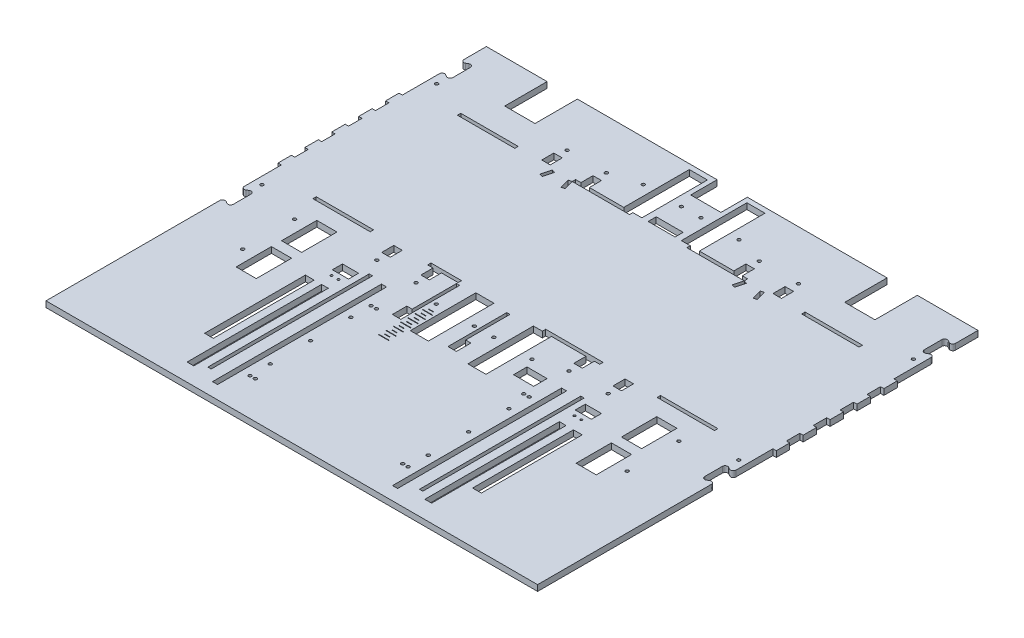
SolidWorks part; units mm, degrees
note: The reader was unsure of these and kept them because the rebuilt part matched: shared geometry of "Sketch11<3>".
material "Acrylic (Medium-high impact)"
ref_plane "Front Plane" through (0, 0, 0) normal (0, 0, 1) x (1, 0, 0)
ref_plane "Top Plane" through (0, 0, 0) normal (0, 1, 0) x (1, 0, 0)
ref_plane "Right Plane" through (0, 0, 0) normal (1, 0, 0) x (0, 0, -1)
sketch "Sketch1" plane through (0, 0, 0) normal (0, 1, 0) x (1, 0, 0)
  line L0 (0, 136.525) -> (0, -165.1) construction
  line L1 (-406.4, 136.525) -> (406.4, 136.525)
  line L2 (-406.4, 136.525) -> (-406.4, -165.1)
  line L3 (-406.4, -165.1) -> (406.4, -165.1)
  line L4 (406.4, 136.525) -> (406.4, -165.1)
  line L5 (-352.2133, 69.85) -> (-352.2133, 66.675)
  line L6 (-406.4, 69.85) -> (-352.2133, 69.85)
  line L7 (-406.4, 69.85) -> (-406.4, 66.675)
  line L8 (-406.4, 66.675) -> (-352.2133, 66.675)
  line L9 (-352.2133, 69.85) -> (-352.2133, 66.675)
  line L10 (-406.4, -66.675) -> (-352.2133, -66.675)
  line L11 (-406.4, -66.675) -> (-406.4, -69.85)
  line L12 (-406.4, -69.85) -> (-352.2133, -69.85)
  line L13 (-352.2133, -66.675) -> (-352.2133, -69.85)
  line L14 (-352.2133, 69.85) -> (-298.0267, 69.85)
  line L15 (-298.0267, 69.85) -> (-298.0267, 66.675)
  line L16 (-352.2133, 66.675) -> (-298.0267, 66.675)
  line L17 (-352.2133, -66.675) -> (-352.2133, -69.85)
  line L18 (-352.2133, -66.675) -> (-298.0267, -66.675)
  line L19 (-298.0267, -66.675) -> (-298.0267, -69.85)
  line L20 (-352.2133, -69.85) -> (-298.0267, -69.85)
  line L21 (-298.0267, 69.85) -> (-298.0267, 66.675)
  line L22 (-298.0267, 69.85) -> (-243.84, 69.85)
  line L23 (-243.84, 69.85) -> (-243.84, 66.675)
  line L24 (-298.0267, 66.675) -> (-243.84, 66.675)
  line L25 (-298.0267, -66.675) -> (-298.0267, -69.85)
  line L26 (-298.0267, -66.675) -> (-243.84, -66.675)
  line L27 (-243.84, -66.675) -> (-243.84, -69.85)
  line L28 (-298.0267, -69.85) -> (-243.84, -69.85)
  line L29 (-243.84, 69.85) -> (-243.84, 66.675)
  line L30 (-243.84, 69.85) -> (-189.6533, 69.85)
  line L31 (-189.6533, 69.85) -> (-189.6533, 66.675)
  line L32 (-243.84, 66.675) -> (-189.6533, 66.675)
  line L33 (-243.84, -66.675) -> (-243.84, -69.85)
  line L34 (-243.84, -66.675) -> (-189.6533, -66.675)
  line L35 (-189.6533, -66.675) -> (-189.6533, -69.85)
  line L36 (-243.84, -69.85) -> (-189.6533, -69.85)
  line L37 (-189.6533, 69.85) -> (-189.6533, 66.675)
  line L38 (-189.6533, 69.85) -> (-135.4667, 69.85)
  line L39 (-135.4667, 69.85) -> (-135.4667, 66.675)
  line L40 (-189.6533, 66.675) -> (-135.4667, 66.675)
  line L41 (-189.6533, -66.675) -> (-189.6533, -69.85)
  line L42 (-189.6533, -66.675) -> (-135.4667, -66.675)
  line L43 (-135.4667, -66.675) -> (-135.4667, -69.85)
  line L44 (-189.6533, -69.85) -> (-135.4667, -69.85)
  line L45 (-135.4667, 69.85) -> (-135.4667, 66.675)
  line L46 (-135.4667, 69.85) -> (-81.28, 69.85)
  line L47 (-81.28, 69.85) -> (-81.28, 66.675)
  line L48 (-135.4667, 66.675) -> (-81.28, 66.675)
  line L49 (-135.4667, -66.675) -> (-135.4667, -69.85)
  line L50 (-135.4667, -66.675) -> (-81.28, -66.675)
  line L51 (-81.28, -66.675) -> (-81.28, -69.85)
  line L52 (-135.4667, -69.85) -> (-81.28, -69.85)
  line L53 (-81.28, 69.85) -> (-81.28, 66.675)
  line L54 (-81.28, 69.85) -> (-27.0933, 69.85)
  line L55 (-27.0933, 69.85) -> (-27.0933, 66.675)
  line L56 (-81.28, 66.675) -> (-27.0933, 66.675)
  line L57 (-81.28, -66.675) -> (-81.28, -69.85)
  line L58 (-81.28, -66.675) -> (-27.0933, -66.675)
  line L59 (-27.0933, -66.675) -> (-27.0933, -69.85)
  line L60 (-81.28, -69.85) -> (-27.0933, -69.85)
  line L61 (-27.0933, 69.85) -> (-27.0933, 66.675)
  line L62 (-27.0933, 69.85) -> (27.0933, 69.85)
  line L63 (27.0933, 69.85) -> (27.0933, 66.675)
  line L64 (-27.0933, 66.675) -> (27.0933, 66.675)
  line L65 (-27.0933, -66.675) -> (-27.0933, -69.85)
  line L66 (-27.0933, -66.675) -> (27.0933, -66.675)
  line L67 (27.0933, -66.675) -> (27.0933, -69.85)
  line L68 (-27.0933, -69.85) -> (27.0933, -69.85)
  line L69 (27.0933, 69.85) -> (27.0933, 66.675)
  line L70 (27.0933, 69.85) -> (81.28, 69.85)
  line L71 (81.28, 69.85) -> (81.28, 66.675)
  line L72 (27.0933, 66.675) -> (81.28, 66.675)
  line L73 (27.0933, -66.675) -> (27.0933, -69.85)
  line L74 (27.0933, -66.675) -> (81.28, -66.675)
  line L75 (81.28, -66.675) -> (81.28, -69.85)
  line L76 (27.0933, -69.85) -> (81.28, -69.85)
  line L77 (81.28, 69.85) -> (81.28, 66.675)
  line L78 (81.28, 69.85) -> (135.4667, 69.85)
  line L79 (135.4667, 69.85) -> (135.4667, 66.675)
  line L80 (81.28, 66.675) -> (135.4667, 66.675)
  line L81 (81.28, -66.675) -> (81.28, -69.85)
  line L82 (81.28, -66.675) -> (135.4667, -66.675)
  line L83 (135.4667, -66.675) -> (135.4667, -69.85)
  line L84 (81.28, -69.85) -> (135.4667, -69.85)
  line L85 (135.4667, 69.85) -> (135.4667, 66.675)
  line L86 (135.4667, 69.85) -> (189.6533, 69.85)
  line L87 (189.6533, 69.85) -> (189.6533, 66.675)
  line L88 (135.4667, 66.675) -> (189.6533, 66.675)
  line L89 (135.4667, -66.675) -> (135.4667, -69.85)
  line L90 (135.4667, -66.675) -> (189.6533, -66.675)
  line L91 (189.6533, -66.675) -> (189.6533, -69.85)
  line L92 (135.4667, -69.85) -> (189.6533, -69.85)
  line L93 (189.6533, 69.85) -> (189.6533, 66.675)
  line L94 (189.6533, 69.85) -> (243.84, 69.85)
  line L95 (243.84, 69.85) -> (243.84, 66.675)
  line L96 (189.6533, 66.675) -> (243.84, 66.675)
  line L97 (189.6533, -66.675) -> (189.6533, -69.85)
  line L98 (189.6533, -66.675) -> (243.84, -66.675)
  line L99 (243.84, -66.675) -> (243.84, -69.85)
  line L100 (189.6533, -69.85) -> (243.84, -69.85)
  line L101 (243.84, 69.85) -> (243.84, 66.675)
  line L102 (243.84, 69.85) -> (298.0267, 69.85)
  line L103 (298.0267, 69.85) -> (298.0267, 66.675)
  line L104 (243.84, 66.675) -> (298.0267, 66.675)
  line L105 (243.84, -66.675) -> (243.84, -69.85)
  line L106 (243.84, -66.675) -> (298.0267, -66.675)
  line L107 (298.0267, -66.675) -> (298.0267, -69.85)
  line L108 (243.84, -69.85) -> (298.0267, -69.85)
  line L109 (298.0267, 69.85) -> (298.0267, 66.675)
  line L110 (298.0267, 69.85) -> (352.2133, 69.85)
  line L111 (352.2133, 69.85) -> (352.2133, 66.675)
  line L112 (298.0267, 66.675) -> (352.2133, 66.675)
  line L113 (298.0267, -66.675) -> (298.0267, -69.85)
  line L114 (298.0267, -66.675) -> (352.2133, -66.675)
  line L115 (352.2133, -66.675) -> (352.2133, -69.85)
  line L116 (298.0267, -69.85) -> (352.2133, -69.85)
  line L117 (352.2133, 69.85) -> (352.2133, 66.675)
  line L118 (352.2133, 69.85) -> (406.4, 69.85)
  line L119 (406.4, 69.85) -> (406.4, 66.675)
  line L120 (352.2133, 66.675) -> (406.4, 66.675)
  line L121 (352.2133, -66.675) -> (352.2133, -69.85)
  line L122 (352.2133, -66.675) -> (406.4, -66.675)
  line L123 (406.4, -66.675) -> (406.4, -69.85)
  line L124 (352.2133, -69.85) -> (406.4, -69.85)
  line L125 (-54.1867, 66.675) -> (-54.1867, -66.675) construction
  line L126 (-381, 57.15) -> (-381, 44.45)
  line L127 (-381, 69.85) -> (-377.825, 69.85)
  line L128 (-381, 69.85) -> (-381, 57.15)
  line L129 (-381, 57.15) -> (-377.825, 57.15)
  line L130 (-377.825, 69.85) -> (-377.825, 57.15)
  line L131 (377.825, 69.85) -> (381, 69.85)
  line L132 (377.825, 69.85) -> (377.825, 57.15)
  line L133 (377.825, 57.15) -> (381, 57.15)
  line L134 (381, 69.85) -> (381, 57.15)
  line L135 (-381, 57.15) -> (-377.825, 57.15)
  line L136 (-377.825, 57.15) -> (-377.825, 44.45)
  line L137 (-381, 44.45) -> (-377.825, 44.45)
  line L138 (377.825, 57.15) -> (377.825, 44.45)
  line L139 (377.825, 57.15) -> (381, 57.15)
  line L140 (381, 57.15) -> (381, 44.45)
  line L141 (377.825, 44.45) -> (381, 44.45)
  line L142 (-381, 44.45) -> (-381, 31.75)
  line L143 (-381, 44.45) -> (-377.825, 44.45)
  line L144 (-377.825, 44.45) -> (-377.825, 31.75)
  line L145 (-381, 31.75) -> (-377.825, 31.75)
  line L146 (377.825, 44.45) -> (377.825, 31.75)
  line L147 (377.825, 44.45) -> (381, 44.45)
  line L148 (381, 44.45) -> (381, 31.75)
  line L149 (377.825, 31.75) -> (381, 31.75)
  line L150 (-381, 31.75) -> (-381, 19.05)
  line L151 (-381, 31.75) -> (-377.825, 31.75)
  line L152 (-377.825, 31.75) -> (-377.825, 19.05)
  line L153 (-381, 19.05) -> (-377.825, 19.05)
  line L154 (377.825, 31.75) -> (377.825, 19.05)
  line L155 (377.825, 31.75) -> (381, 31.75)
  line L156 (381, 31.75) -> (381, 19.05)
  line L157 (377.825, 19.05) -> (381, 19.05)
  line L158 (-381, 19.05) -> (-381, 6.35)
  line L159 (-381, 19.05) -> (-377.825, 19.05)
  line L160 (-377.825, 19.05) -> (-377.825, 6.35)
  line L161 (-381, 6.35) -> (-377.825, 6.35)
  line L162 (377.825, 19.05) -> (377.825, 6.35)
  line L163 (377.825, 19.05) -> (381, 19.05)
  line L164 (381, 19.05) -> (381, 6.35)
  line L165 (377.825, 6.35) -> (381, 6.35)
  line L166 (-381, 6.35) -> (-381, -6.35)
  line L167 (-381, 6.35) -> (-377.825, 6.35)
  line L168 (-377.825, 6.35) -> (-377.825, -6.35)
  line L169 (-381, -6.35) -> (-377.825, -6.35)
  line L170 (377.825, 6.35) -> (377.825, -6.35)
  line L171 (377.825, 6.35) -> (381, 6.35)
  line L172 (381, 6.35) -> (381, -6.35)
  line L173 (377.825, -6.35) -> (381, -6.35)
  line L174 (-381, -6.35) -> (-381, -19.05)
  line L175 (-381, -6.35) -> (-377.825, -6.35)
  line L176 (-377.825, -6.35) -> (-377.825, -19.05)
  line L177 (-381, -19.05) -> (-377.825, -19.05)
  line L178 (377.825, -6.35) -> (377.825, -19.05)
  line L179 (377.825, -6.35) -> (381, -6.35)
  line L180 (381, -6.35) -> (381, -19.05)
  line L181 (377.825, -19.05) -> (381, -19.05)
  line L182 (-381, -19.05) -> (-381, -31.75)
  line L183 (-381, -19.05) -> (-377.825, -19.05)
  line L184 (-377.825, -19.05) -> (-377.825, -31.75)
  line L185 (-381, -31.75) -> (-377.825, -31.75)
  line L186 (377.825, -19.05) -> (377.825, -31.75)
  line L187 (377.825, -19.05) -> (381, -19.05)
  line L188 (381, -19.05) -> (381, -31.75)
  line L189 (377.825, -31.75) -> (381, -31.75)
  line L190 (-381, -31.75) -> (-381, -44.45)
  line L191 (-381, -31.75) -> (-377.825, -31.75)
  line L192 (-377.825, -31.75) -> (-377.825, -44.45)
  line L193 (-381, -44.45) -> (-377.825, -44.45)
  line L194 (377.825, -31.75) -> (377.825, -44.45)
  line L195 (377.825, -31.75) -> (381, -31.75)
  line L196 (381, -31.75) -> (381, -44.45)
  line L197 (377.825, -44.45) -> (381, -44.45)
  line L198 (-381, -44.45) -> (-381, -57.15)
  line L199 (-381, -44.45) -> (-377.825, -44.45)
  line L200 (-377.825, -44.45) -> (-377.825, -57.15)
  line L201 (-381, -57.15) -> (-377.825, -57.15)
  line L202 (377.825, -44.45) -> (377.825, -57.15)
  line L203 (377.825, -44.45) -> (381, -44.45)
  line L204 (381, -44.45) -> (381, -57.15)
  line L205 (377.825, -57.15) -> (381, -57.15)
  line L206 (-381, -57.15) -> (-381, -69.85)
  line L207 (-381, -57.15) -> (-377.825, -57.15)
  line L208 (-377.825, -57.15) -> (-377.825, -69.85)
  line L209 (-381, -69.85) -> (-377.825, -69.85)
  line L210 (377.825, -57.15) -> (377.825, -69.85)
  line L211 (377.825, -57.15) -> (381, -57.15)
  line L212 (381, -57.15) -> (381, -69.85)
  line L213 (377.825, -69.85) -> (381, -69.85)
  line L214 (-377.825, 0) -> (377.825, 0) construction
  point P23 (-54.1867, 0)
  point P133 (0, 0)
  dimension "D1" = 301.625
  dimension "D2" = 812.8
  dimension "D3" = 3.175
  dimension "D5" = 54.1867
  dimension "D6" = 66.675
  dimension "D7" = 133.35
  dimension "D9" = 12.7
  dimension "D10" = 755.65
  dimension "D4" = 15
  dimension "D8" = 11
extrude "Main Extrude" add sketch "Sketch1" along normal blind 5.588 contours L124 L116 L108 L100 L92 L84 L76 L68 L60 L52 L44 L36 L28 L20 L12 L2 L3 L4 | L210 L202 L194 L186 L178 L170 L162 L154 L146 L138 L132 L120 L112 L104 L96 L88 L80 L72 L64 L56 L48 L40 L32 L24 L16 L8 L130 L136 L144 L152 L160 L168 L176 L184 L192 L200 L208 L10 L18 L26 L34 L42 L50 L58 L66 L74 L82 L90 L98 L106 L114 | L110 L118 L4 L1 L2 L6 L14 L22 L30 L38 L46 L54 L62 L70 L78 L86 L94 L102 | L206 L198 L190 L182 L174 L166 L158 L150 L142 L126 L128 L8 L2 L10 | L204 L212 L122 L4 L120 L134 L140 L148 L156 L164 L172 L180 L188 L196 | L126 L137 L136 L129 | L150 L153 L152 L145 | L166 L169 L168 L161 | L182 L185 L184 L177 | L198 L201 L200 L193 | L13 L20 L19 L18 | L5 L16 L15 L14 | L23 L32 L31 L30 | L27 L36 L35 L34 | L43 L52 L51 L50 | L39 L48 L47 L46 | L55 L64 L63 L62 | L59 L68 L67 L66 | L71 L80 L79 L78 | L75 L84 L83 L82 | L87 L96 L95 L94 | L103 L112 L111 L110 | L91 L100 L99 L98 | L107 L116 L115 L114 | L138 L141 L140 L133 | L154 L157 L156 L149 | L170 L173 L172 L165 | L186 L189 L188 L181 | L202 L205 L204 L197
sketch "Sketch2" plane through (0, 5.588, 0) normal (0, 1, 0) x (1, 0, 0)
  line L0 (-90.678, 66.675) -> (-90.678, -110.1521) construction
  line L1 (-81.28, 66.675) -> (-27.0933, 66.675) construction
  line L3 (90.678, 66.675) -> (90.678, -110.1521) construction
  line L4 (27.0933, 66.675) -> (81.28, 66.675) construction
  line L5 (-90.678, -21.7386) -> (90.678, -21.7386) construction
  line L6 (-81.28, -66.675) -> (-27.0933, -66.675) construction
  line L7 (-52.578, -66.675) -> (-1.778, -66.675) construction
  line L8 (-52.578, -66.675) -> (-52.578, -36.2354) construction
  line L9 (-52.578, -36.2354) -> (-1.778, -36.2354) construction
  line L10 (-1.778, -66.675) -> (-1.778, -36.2354) construction
  line L11 (-26.543, 63.5) -> (26.543, 63.5) construction
  line L12 (13.843, -60.325) -> (40.513, -60.325) construction
  line L13 (13.843, -60.325) -> (13.843, -66.675) construction
  line L14 (13.843, -66.675) -> (40.513, -66.675) construction
  line L15 (40.513, -60.325) -> (40.513, -66.675) construction
  line L16 (-53.213, 66.675) -> (-26.543, 66.675) construction
  line L17 (-53.213, 66.675) -> (-53.213, 60.325) construction
  line L18 (-53.213, 60.325) -> (-26.543, 60.325) construction
  line L19 (-26.543, 66.675) -> (-26.543, 60.325) construction
  line L20 (26.543, 66.675) -> (53.213, 66.675) construction
  line L21 (26.543, 66.675) -> (26.543, 60.325) construction
  line L22 (26.543, 60.325) -> (53.213, 60.325) construction
  line L23 (53.213, 66.675) -> (53.213, 60.325) construction
  line L24 (27.0933, -66.675) -> (81.28, -66.675) construction
  point P4 (0, -21.7386)
  point P23 (-27.178, -36.2354)
  point P24 (27.178, -60.325)
  point P34 (0, 63.5)
  point P35 (-39.878, 66.675)
  dimension "D1" = 181.356
  dimension "D2" = 50.8
  dimension "D3" = 63.5
  dimension "D4" = 26.67
  dimension "D5" = 63.5
  dimension "D6" = 50.8
  dimension "D7" = 6.35
sketch "Sketch3" plane through (0, 5.588, 0) normal (0, 1, 0) x (1, 0, 0)
  line L1 (-52.578, -66.675) -> (-27.0933, -66.675)
  line L2 (-52.578, -66.675) -> (-52.578, -69.85)
  line L3 (-52.578, -69.85) -> (-27.0933, -69.85)
  line L4 (-27.0933, -66.675) -> (-27.0933, -69.85)
extrude "Under Trough Fill" add sketch "Sketch3" against normal up to surface (5.588 mm away) up to face at (0, 0, 1.5875)
sketch "Sketch4" plane through (0, 5.588, 0) normal (0, 1, 0) x (1, 0, 0)
  line L0 (-27.178, 66.675) -> (27.178, 66.675) construction
  line L2 (-406.4, 136.525) -> (406.4, 136.525) construction
  line L3 (27.0933, -69.85) -> (81.28, -69.85) construction
  line L4 (27.0933, 66.675) -> (81.28, 66.675) construction
  line L5 (27.178, -131.7625) -> (27.178, -66.675) construction
  line L6 (13.843, -66.675) -> (40.513, -66.675) construction
  line L7 (27.178, 131.7625) -> (27.178, 66.675) construction
  line L8 (-406.4, 66.675) -> (-406.4, -66.675) construction
  line L9 (-27.178, 131.7625) -> (-27.178, 66.675) construction
  line L11 (-406.4, -66.675) -> (-381, -66.675) construction
  line L12 (-400.05, -66.675) -> (-387.35, -66.675)
  line L13 (-400.05, -66.675) -> (-400.05, -63.5)
  line L14 (-400.05, -63.5) -> (-387.35, -63.5)
  line L15 (-387.35, -66.675) -> (-387.35, -63.5)
  line L16 (-406.4, 66.675) -> (-381, 66.675) construction
  line L17 (-400.05, 66.675) -> (-387.35, 66.675)
  line L18 (-400.05, 66.675) -> (-400.05, 63.5)
  line L19 (-400.05, 63.5) -> (-387.35, 63.5)
  line L20 (-387.35, 66.675) -> (-387.35, 63.5)
  line L21 (381, 66.675) -> (406.4, 66.675) construction
  line L22 (387.35, 66.675) -> (400.05, 66.675)
  line L23 (387.35, 66.675) -> (387.35, 63.5)
  line L24 (387.35, 63.5) -> (400.05, 63.5)
  line L25 (400.05, 66.675) -> (400.05, 63.5)
  line L26 (381, -66.675) -> (406.4, -66.675) construction
  line L27 (387.35, -66.675) -> (400.05, -66.675)
  line L28 (387.35, -66.675) -> (387.35, -63.5)
  line L29 (387.35, -63.5) -> (400.05, -63.5)
  line L30 (400.05, -66.675) -> (400.05, -63.5)
  line L35 (406.4, 66.675) -> (406.4, -66.675) construction
  line L36 (-81.28, 69.85) -> (-27.0933, 69.85) construction
  line L39 (27.0933, 69.85) -> (81.28, 69.85) construction
  line L40 (18.628, -69.85) -> (35.728, -69.85)
  line L41 (18.628, -69.85) -> (18.628, -131.7625)
  line L42 (18.628, -131.7625) -> (35.728, -131.7625)
  line L43 (35.728, -69.85) -> (35.728, -131.7625)
  line L44 (18.628, 131.7625) -> (35.728, 131.7625)
  line L45 (18.628, 131.7625) -> (18.628, 69.85)
  line L46 (18.628, 69.85) -> (35.728, 69.85)
  line L47 (35.728, 131.7625) -> (35.728, 69.85)
  line L48 (9.178, -97.7625) -> (45.178, -97.7625) construction
  line L49 (-35.728, 131.7625) -> (-18.628, 131.7625)
  line L50 (-35.728, 131.7625) -> (-35.728, 69.85)
  line L51 (-35.728, 69.85) -> (-18.628, 69.85)
  line L52 (-18.628, 131.7625) -> (-18.628, 69.85)
  line L53 (-45.178, 97.7625) -> (-9.178, 97.7625) construction
  line L54 (9.178, 97.7625) -> (45.178, 97.7625) construction
  circle A12 centre (9.178, -97.7625) radius 1.5
  circle A13 centre (45.178, -97.7625) radius 1.5
  circle A14 centre (9.178, 97.7625) radius 1.5
  circle A15 centre (45.178, 97.7625) radius 1.5
  circle A16 centre (-9.178, 97.7625) radius 1.5
  circle A17 centre (-45.178, 97.7625) radius 1.5
  point P2 (0, 136.525)
  point P3 (0, 66.675)
  point P59 (-393.7, -63.5)
  point P62 (393.7, -66.675)
  point P73 (27.178, -69.85)
  point P87 (27.178, 131.7625)
  point P92 (-27.178, 131.7625)
  point P100 (27.178, -97.7625)
  point P106 (-27.178, 97.7625)
  point P107 (27.178, 97.7625)
  dimension "D2" = 37.256
  dimension "D15" = 3
  dimension "D4" = 12.7
  dimension "D5" = 3.175
  dimension "D6" = 12.7
  dimension "D7" = 12.7
  dimension "D12" = 17.1
  dimension "D13" = 61.9125
  dimension "D14" = 36
  dimension "D16" = 27.9125
  dimension "D17" = 27.9125
extrude "Lever Holes" cut sketch "Sketch4" against normal through all
sketch "Sketch5" plane through (0, 5.588, 0) normal (0, 1, 0) x (1, 0, 0)
  line L0 (-27.178, -131.7625) -> (-27.178, -69.85) construction
  line L1 (-49.428, -99.2124) -> (-4.928, -99.2124) construction
  line L2 (-52.428, -127) -> (-49.428, -127)
  line L3 (-52.428, -127) -> (-52.428, -71.4248)
  line L4 (-52.428, -71.4248) -> (-49.428, -71.4248)
  line L5 (-49.428, -127) -> (-49.428, -71.4248)
  line L6 (-4.928, -127) -> (-1.928, -127)
  line L7 (-4.928, -127) -> (-4.928, -71.4248)
  line L8 (-4.928, -71.4248) -> (-1.928, -71.4248)
  line L9 (-1.928, -127) -> (-1.928, -71.4248)
  line L10 (-27.178, -66.675) -> (-27.178, -99.2124) construction
  line L11 (-52.578, -66.675) -> (-1.778, -66.675) construction
  line L12 (-35.728, -69.85) -> (-18.628, -69.85)
  line L13 (-81.28, -69.85) -> (-52.578, -69.85) construction
  line L14 (-55.778, -71.9185) -> (-4.928, -71.9185) construction
  line L15 (-35.728, -69.85) -> (-35.728, -131.7625)
  line L16 (-52.578, -66.675) -> (-52.578, -69.85) construction
  line L17 (-52.428, -127) -> (-57.428, -127)
  line L18 (-52.428, -127) -> (-52.428, -113.3)
  line L19 (-52.428, -113.3) -> (-57.428, -113.3)
  line L20 (-57.428, -127) -> (-57.428, -113.3)
  line L21 (-1.928, -127) -> (3.072, -127)
  line L22 (-1.928, -127) -> (-1.928, -113.3)
  line L23 (-1.928, -113.3) -> (3.072, -113.3)
  line L24 (3.072, -127) -> (3.072, -113.3)
  line L25 (-52.578, -66.675) -> (-52.428, -66.675)
  line L26 (-52.578, -66.675) -> (-52.578, -69.85)
  line L27 (-52.578, -69.85) -> (-52.428, -69.85)
  line L28 (-52.428, -66.675) -> (-52.428, -69.85)
  line L29 (-35.728, -131.7625) -> (-18.628, -131.7625)
  line L30 (-18.628, -69.85) -> (-18.628, -131.7625)
  line L31 (-81.28, -69.85) -> (-52.578, -69.85) construction
  circle A0 centre (-9.178, -97.7625) radius 1.5
  circle A2 centre (-45.178, -97.7625) radius 1.5
  point P19 (-50.928, -127)
  point P20 (-3.428, -127)
  dimension "D6" = 3
  dimension "D1" = 3
  dimension "D3" = 47.5
  dimension "D4" = 57.15
  dimension "D7" = 5
  dimension "D8" = 13.7
  dimension "D2" = 1.5748
  dimension "D5" = 17.1
  dimension "D9" = 61.9125
  dimension "D10" = 13.7
  dimension "D11" = 9.45
  dimension "D12" = 34
extrude "Trough Slot" cut sketch "Sketch5" against normal through all
sketch "Sketch6" plane through (0, 5.588, 0) normal (0, 1, 0) x (1, 0, 0)
  line L0 (90.678, -130.35) -> (103.378, -130.35) construction
  line L1 (-114.6905, -123.85) -> (114.6905, -123.85) construction
  line L3 (-81.28, -69.85) -> (-52.428, -69.85) construction
  line L4 (111.4405, -123.85) -> (117.9405, -123.85) construction
  line L5 (95.4405, -130.35) -> (95.4405, -83.0238) construction
  line L6 (90.678, 66.675) -> (90.678, -110.1521) construction
  line L7 (0, -21.7386) -> (0, -165.1) construction
  line L8 (-90.678, -21.7386) -> (90.678, -21.7386) construction
  line L9 (-406.4, -165.1) -> (406.4, -165.1) construction
  line L20 (-117.9405, -123.85) -> (-111.4405, -123.85) construction
  line L21 (-122.3105, -109.245) -> (-107.0705, -109.245)
  line L22 (-122.3105, -109.245) -> (-122.3105, -118.77)
  line L23 (-122.3105, -118.77) -> (-107.0705, -118.77)
  line L24 (-107.0705, -109.245) -> (-107.0705, -118.77)
  line L25 (107.0705, -109.245) -> (122.3105, -109.245)
  line L26 (107.0705, -109.245) -> (107.0705, -118.77)
  line L27 (107.0705, -118.77) -> (122.3105, -118.77)
  line L28 (122.3105, -109.245) -> (122.3105, -118.77)
  line L29 (-114.6905, -118.77) -> (-114.6905, -123.85) construction
  line L30 (114.6905, -118.77) -> (114.6905, -123.85) construction
  circle A0 centre (117.9405, -123.85) radius 1.05
  circle A1 centre (111.4405, -123.85) radius 1.05
  circle A10 centre (-117.9405, -123.85) radius 1.05
  circle A11 centre (-111.4405, -123.85) radius 1.05
  point P0 (108.1405, -130.35)
  point P11 (0, -123.85)
  dimension "D5" = 2.1
  dimension "D2" = 60.5
  dimension "D3" = 6.5
  dimension "D4" = 12.7
  dimension "D6" = 6.5
  dimension "D7" = 4.7625
  dimension "D8" = 3.3
  dimension "D9" = 5.08
  dimension "D10" = 9.525
  dimension "D11" = 15.24
extrude "Close Switch Holes" cut sketch "Sketch6" against normal through all
sketch "Sketch7" plane through (0, 5.588, 0) normal (0, 1, 0) x (1, 0, 0)
  line L0 (-42.578, -149.85) -> (-42.578, -105.4) construction
  line L1 (-49.428, -127) -> (-35.728, -127) construction
  line L2 (-49.428, -127) -> (-49.428, -71.4248) construction
  line L4 (-35.728, -69.85) -> (-35.728, -131.7625) construction
  line L9 (-81.28, -69.85) -> (-52.428, -69.85) construction
  line L10 (-47.3405, -142.738) -> (-47.3405, -143.246)
  line L15 (-47.3405, -149.596) -> (-37.8155, -149.596)
  line L16 (-47.3405, -149.596) -> (-47.3405, -150.104)
  line L21 (-47.3405, -150.104) -> (-37.8155, -150.104)
  line L22 (-37.8155, -149.596) -> (-37.8155, -150.104)
  line L27 (-47.3405, -149.596) -> (-37.8155, -150.104) construction
  line L28 (-47.3405, -150.104) -> (-37.8155, -149.596) construction
  line L33 (-44.9592, -146.421) -> (-40.1967, -146.421)
  line L34 (-44.9592, -146.421) -> (-44.9592, -146.929)
  line L39 (-44.9592, -146.929) -> (-40.1967, -146.929)
  line L40 (-40.1967, -146.421) -> (-40.1967, -146.929)
  line L45 (-44.9592, -146.421) -> (-40.1967, -146.929) construction
  line L46 (-44.9592, -146.929) -> (-40.1967, -146.421) construction
  line L51 (-47.3405, -142.738) -> (-37.8155, -142.738)
  line L52 (-37.8155, -142.738) -> (-37.8155, -143.246)
  line L57 (-47.3405, -143.246) -> (-37.8155, -143.246)
  line L58 (-44.9592, -139.563) -> (-44.9592, -140.071)
  line L63 (-44.9592, -139.563) -> (-40.1967, -139.563)
  line L64 (-40.1967, -139.563) -> (-40.1967, -140.071)
  line L69 (-44.9592, -140.071) -> (-40.1967, -140.071)
  line L70 (-47.3405, -135.88) -> (-47.3405, -136.388)
  line L75 (-47.3405, -135.88) -> (-37.8155, -135.88)
  line L76 (-37.8155, -135.88) -> (-37.8155, -136.388)
  line L81 (-47.3405, -136.388) -> (-37.8155, -136.388)
  line L82 (-44.9592, -132.705) -> (-44.9592, -133.213)
  line L83 (-44.9592, -132.705) -> (-40.1967, -132.705)
  line L84 (-40.1967, -132.705) -> (-40.1967, -133.213)
  line L85 (-44.9592, -133.213) -> (-40.1967, -133.213)
  line L86 (-47.3405, -129.022) -> (-47.3405, -129.53)
  line L87 (-47.3405, -129.022) -> (-37.8155, -129.022)
  line L88 (-37.8155, -129.022) -> (-37.8155, -129.53)
  line L89 (-47.3405, -129.53) -> (-37.8155, -129.53)
  line L90 (-44.9593, -125.847) -> (-44.9593, -126.355)
  line L91 (-44.9593, -125.847) -> (-40.1968, -125.847)
  line L92 (-40.1968, -125.847) -> (-40.1968, -126.355)
  line L93 (-44.9593, -126.355) -> (-40.1968, -126.355)
  line L94 (-47.3405, -122.164) -> (-47.3405, -122.672)
  line L95 (-47.3405, -122.164) -> (-37.8155, -122.164)
  line L96 (-37.8155, -122.164) -> (-37.8155, -122.672)
  line L97 (-47.3405, -122.672) -> (-37.8155, -122.672)
  line L98 (-44.9593, -118.989) -> (-44.9593, -119.497)
  line L99 (-44.9593, -118.989) -> (-40.1968, -118.989)
  line L100 (-40.1968, -118.989) -> (-40.1968, -119.497)
  line L101 (-44.9593, -119.497) -> (-40.1968, -119.497)
  line L102 (-47.3405, -115.306) -> (-47.3405, -115.814)
  line L103 (-47.3405, -115.306) -> (-37.8155, -115.306)
  line L104 (-37.8155, -115.306) -> (-37.8155, -115.814)
  line L105 (-47.3405, -115.814) -> (-37.8155, -115.814)
  line L106 (-44.9593, -112.131) -> (-44.9593, -112.639)
  line L107 (-44.9593, -112.131) -> (-40.1968, -112.131)
  line L108 (-40.1968, -112.131) -> (-40.1968, -112.639)
  line L109 (-44.9593, -112.639) -> (-40.1968, -112.639)
  line L130 (-28.5048, -105.4) -> (-42.578, -105.4) construction
  line L136 (-47.3405, -108.448) -> (-47.3405, -108.956)
  line L137 (-47.3405, -108.448) -> (-37.8155, -108.448)
  line L138 (-37.8155, -108.448) -> (-37.8155, -108.956)
  line L139 (-47.3405, -108.956) -> (-37.8155, -108.956)
  line L140 (-44.9593, -105.273) -> (-44.9593, -105.781)
  line L141 (-44.9593, -105.273) -> (-40.1968, -105.273)
  line L142 (-40.1968, -105.273) -> (-40.1968, -105.781)
  line L143 (-44.9593, -105.781) -> (-40.1968, -105.781)
  point P2 (-42.578, -146.675)
  point P16 (-44.9592, -146.675)
  point P17 (-47.3405, -149.85)
  point P65 (-42.578, -127)
  dimension "D1" = 80
  dimension "D2" = 44.45
  dimension "D3" = 0.508
  dimension "D4" = 9.525
  dimension "D5" = 3.175
  dimension "D6" = 4.7625
  dimension "D8" = 3.175
  dimension "D7" = 7
extrude "Trough Measurement" cut sketch "Sketch7" against normal through all
sketch "Sketch8" plane through (0, 5.588, 0) normal (0, 1, 0) x (1, 0, 0)
  line L0 (160.528, 96.525) -> (160.528, -85.725) construction
  line L1 (49.063, -106.3625) -> (68.113, -106.3625)
  line L2 (49.063, -106.3625) -> (49.063, -119.0625)
  line L3 (49.063, -119.0625) -> (68.113, -119.0625)
  line L4 (68.113, -106.3625) -> (68.113, -119.0625)
  line L5 (35.728, -131.7625) -> (35.728, -69.85) construction
  line L6 (135.4667, -69.85) -> (189.6533, -69.85) construction
  line L15 (-406.4, 136.525) -> (406.4, 136.525) construction
  line L16 (-18.628, 123) -> (18.628, 123) construction
  line L17 (-18.628, 69.85) -> (-18.628, 131.7625) construction
  line L18 (18.628, 131.7625) -> (18.628, 69.85) construction
  line L19 (0, 77.47) -> (0, 96.525) construction
  line L20 (18.628, -131.7625) -> (35.728, -131.7625) construction
  line L29 (151.003, -119.0625) -> (170.053, -119.0625)
  line L30 (-174.8155, 136.525) -> (-146.2405, 136.525)
  line L31 (-14.2875, 136.525) -> (14.2875, 136.525)
  line L32 (-14.2875, 136.525) -> (-14.2875, 96.525)
  line L33 (-14.2875, 96.525) -> (14.2875, 96.525)
  line L34 (14.2875, 136.525) -> (14.2875, 96.525)
  line L35 (-12.7, 69.85) -> (12.7, 69.85)
  line L36 (-12.7, 69.85) -> (-12.7, 77.47)
  line L37 (-12.7, 77.47) -> (12.7, 77.47)
  line L38 (12.7, 69.85) -> (12.7, 77.47)
  line L39 (-27.0933, 69.85) -> (-18.628, 69.85) construction
  line L40 (151.003, -85.725) -> (170.053, -85.725)
  line L41 (151.003, -85.725) -> (151.003, -161.925)
  line L42 (151.003, -161.925) -> (170.053, -161.925)
  line L43 (170.053, -85.725) -> (170.053, -161.925)
  line L44 (-170.053, -85.725) -> (-151.003, -85.725)
  line L45 (-170.053, -85.725) -> (-170.053, -161.925)
  line L46 (-170.053, -161.925) -> (-151.003, -161.925)
  line L47 (-151.003, -85.725) -> (-151.003, -161.925)
  line L48 (90.678, 66.675) -> (90.678, -110.1521) construction
  line L49 (-151.003, -123.825) -> (151.003, -123.825) construction
  line L50 (151.003, -119.0625) -> (151.003, -128.5875)
  line L51 (151.003, -128.5875) -> (170.053, -128.5875)
  line L52 (170.053, -119.0625) -> (170.053, -128.5875)
  line L53 (-170.053, -119.0625) -> (-151.003, -119.0625)
  line L54 (-170.053, -119.0625) -> (-170.053, -128.5875)
  line L55 (-170.053, -128.5875) -> (-151.003, -128.5875)
  line L56 (-151.003, -119.0625) -> (-151.003, -128.5875)
  line L57 (-174.8155, 136.525) -> (-174.8155, 96.525)
  line L58 (-174.8155, 96.525) -> (-146.2405, 96.525)
  line L59 (-146.2405, 136.525) -> (-146.2405, 96.525)
  line L60 (146.2405, 136.525) -> (174.8155, 136.525)
  line L61 (146.2405, 136.525) -> (146.2405, 96.525)
  line L62 (146.2405, 96.525) -> (174.8155, 96.525)
  line L63 (174.8155, 136.525) -> (174.8155, 96.525)
  line L64 (-160.528, 96.525) -> (-160.528, -85.725) construction
  point P6 (58.588, -106.3625)
  point P23 (0, 123)
  point P30 (170.053, -123.825)
  point P31 (170.053, -123.825)
  point P38 (0, 96.525)
  point P61 (0, -123.825)
  dimension "D1" = 19.05
  dimension "D2" = 12.7
  dimension "D3" = 22.86
  dimension "D4" = 12.7
  dimension "D5" = 9.525
  dimension "D6" = 76.2
  dimension "D8" = 40
  dimension "D9" = 28.575
  dimension "D10" = 7.62
  dimension "D11" = 25.4
  dimension "D12" = 15.875
  dimension "D13" = 60.325
  dimension "D15" = 19.05
extrude "Wire Holes" cut sketch "Sketch8" against normal through all contours L55 L45 L46 L47 | L45 L53 L47 L44 | L51 L41 L42 L43 | L43 L40 L41 L29 | L4 L1 L2 L3 | L34 L31 L32 L33 | L35 L38 L37 L36 | L59 L30 L57 L58 | L63 L60 L61 L62
sketch "Sketch9" plane through (0, 5.588, 0) normal (0, 1, 0) x (1, 0, 0)
  line L0 (-109.2096, 89.85) -> (109.2096, 89.85) construction
  line L1 (109.2096, 89.85) -> (109.2096, -89.85) construction
  line L2 (109.2096, -89.85) -> (-109.2096, -89.85) construction
  line L3 (-109.2096, -89.85) -> (-109.2096, 89.85) construction
  line L4 (-162.56, 66.675) -> (-162.56, -66.675) construction
  line L5 (-189.6533, 66.675) -> (-135.4667, 66.675) construction
  line L6 (-189.6533, -66.675) -> (-135.4667, -66.675) construction
  line L7 (-109.2096, 0) -> (-162.56, 0) construction
  line L8 (-90.678, 66.675) -> (-90.678, -110.1521) construction
  line L9 (-189.6533, -69.85) -> (-135.4667, -69.85) construction
  line L10 (-189.6533, 69.85) -> (-135.4667, 69.85) construction
  line L11 (-113.2096, 69.85) -> (-105.2096, 69.85)
  line L12 (-113.2096, 69.85) -> (-113.2096, 81.28)
  line L13 (-113.2096, 81.28) -> (-105.2096, 81.28)
  line L14 (-105.2096, 69.85) -> (-105.2096, 81.28)
  line L16 (105.2096, 81.28) -> (113.2096, 81.28)
  line L17 (105.2096, 81.28) -> (105.2096, 69.85)
  line L18 (105.2096, 69.85) -> (113.2096, 69.85)
  line L19 (113.2096, 81.28) -> (113.2096, 69.85)
  line L20 (105.2096, -69.85) -> (113.2096, -69.85)
  line L21 (105.2096, -69.85) -> (105.2096, -81.28)
  line L22 (105.2096, -81.28) -> (113.2096, -81.28)
  line L23 (113.2096, -69.85) -> (113.2096, -81.28)
  line L24 (-113.2096, -81.28) -> (-105.2096, -81.28)
  line L25 (-113.2096, -81.28) -> (-113.2096, -69.85)
  line L26 (-113.2096, -69.85) -> (-105.2096, -69.85)
  line L27 (-105.2096, -81.28) -> (-105.2096, -69.85)
  circle A0 centre (109.2096, -89.85) radius 1.5
  circle A1 centre (-109.2096, -89.85) radius 1.5
  circle A2 centre (109.2096, 89.85) radius 1.5
  circle A3 centre (-109.2096, 89.85) radius 1.5
  point P8 (0, -89.85)
  point P29 (-109.2096, 81.28)
  point P43 (109.2096, 81.28)
  point P47 (109.2096, -69.85)
  dimension "D1" = 3
  dimension "D2" = 18.5316
  dimension "D3" = 20
  dimension "D4" = 11.43
  dimension "D5" = 8
extrude "IR Slots" cut sketch "Sketch9" against normal through all
sketch "Sketch10" plane through (0, 5.588, 0) normal (0, 1, 0) x (1, 0, 0)
  line L0 (0, 0) -> (0, 69.85) construction
  line L1 (-100.061, 66.675) -> (-96.9942, 65.8532)
  line L2 (-100.061, 66.675) -> (-102.5263, 57.4746)
  line L3 (-102.5263, 57.4746) -> (-99.4594, 56.6528)
  line L4 (-96.9942, 65.8532) -> (-99.4594, 56.6528)
  line L5 (-84.3618, 65.8532) -> (-81.295, 66.675)
  line L6 (-84.3618, 65.8532) -> (-81.8966, 56.6528)
  line L7 (-81.8966, 56.6528) -> (-78.8297, 57.4746)
  line L8 (-81.295, 66.675) -> (-78.8297, 57.4746)
  line L9 (-12.7, 69.85) -> (12.7, 69.85) construction
  line L14 (81.28, 66.675) -> (100.061, 66.675) construction
  line L19 (-90.678, 66.675) -> (-90.678, -110.1521) construction
  line L20 (-98.2268, 61.253) -> (-83.1292, 61.253) construction
  line L21 (-81.28, 66.675) -> (-100.061, 66.675) construction
  line L22 (98.2268, 61.253) -> (83.1292, 61.253) construction
  line L23 (81.295, 66.675) -> (78.8297, 57.4746)
  line L24 (81.8966, 56.6528) -> (78.8297, 57.4746)
  line L25 (84.3618, 65.8532) -> (81.8966, 56.6528)
  line L26 (84.3618, 65.8532) -> (81.295, 66.675)
  line L27 (96.9942, 65.8532) -> (99.4594, 56.6528)
  line L28 (102.5263, 57.4746) -> (99.4594, 56.6528)
  line L29 (100.061, 66.675) -> (102.5263, 57.4746)
  line L30 (100.061, 66.675) -> (96.9942, 65.8532)
  line L31 (-96.9942, 65.8532) -> (-96.774, 66.675) construction
  line L32 (-84.3618, 65.8532) -> (-84.582, 66.675) construction
  line L33 (-90.678, 66.675) -> (-90.678, 61.253) construction
  line L34 (-96.774, 66.675) -> (-95.9233, 69.85) construction
  line L35 (-84.582, 66.675) -> (-85.4327, 69.85) construction
  line L36 (-81.28, 69.85) -> (-95.9233, 69.85) construction
  point P27 (-90.678, 61.253)
  dimension "D1" = 3.175
  dimension "D3" = 9.525
  dimension "D4" = 105
  dimension "D2" = 6.096
extrude "Door Flange Slots" cut sketch "Sketch10" against normal through all
sketch "Sketch12" plane through (0, 5.588, 0) normal (0, 1, 0) x (1, 0, 0)
  line L0 (-253.5873, 82.55) -> (-225.1393, 82.55) construction
  line L1 (-253.5873, -82.55) -> (-225.1393, -82.55) construction
  line L2 (-233.807, 82.55) -> (-233.807, -82.55) construction
  line L3 (-233.807, 0) -> (0, 0) construction
  line L4 (-298.0267, -69.85) -> (-243.84, -69.85) construction
  line L5 (-240.9508, -76.2) -> (-237.7758, -76.2)
  line L6 (-240.9508, -76.2) -> (-240.9507, -88.9)
  line L7 (-240.9507, -88.9) -> (-237.7758, -88.9)
  line L8 (-237.7758, -76.2) -> (-237.7758, -88.9)
  line L9 (-240.9508, 88.9) -> (-237.7758, 88.9)
  line L10 (-240.9508, 88.9) -> (-240.9508, 76.2)
  line L11 (-240.9508, 76.2) -> (-237.7758, 76.2)
  line L12 (-237.7758, 88.9) -> (-237.7758, 76.2)
  line L13 (0, -3.0734) -> (0, 3.0734) construction
  line L14 (233.807, 82.55) -> (233.807, -82.55) construction
  line L15 (253.5873, -82.55) -> (225.1393, -82.55) construction
  line L16 (253.5873, 82.55) -> (225.1393, 82.55) construction
  line L17 (237.7758, 88.9) -> (237.7758, 76.2)
  line L18 (240.9508, 76.2) -> (237.7758, 76.2)
  line L19 (240.9508, 88.9) -> (240.9508, 76.2)
  line L20 (240.9508, 88.9) -> (237.7758, 88.9)
  line L21 (237.7757, -76.2) -> (237.7757, -88.9)
  line L22 (240.9507, -88.9) -> (237.7757, -88.9)
  line L23 (240.9507, -76.2) -> (240.9507, -88.9)
  line L24 (240.9507, -76.2) -> (237.7757, -76.2)
  circle A0 centre (-253.5873, -82.55) radius 1.5
  circle A1 centre (-225.1393, -82.55) radius 1.5
  circle A2 centre (-253.5873, 82.55) radius 1.5
  circle A3 centre (-225.1393, 82.55) radius 1.5
  circle A4 centre (225.1393, 82.55) radius 1.5
  circle A5 centre (253.5873, 82.55) radius 1.5
  circle A6 centre (225.1393, -82.55) radius 1.5
  circle A7 centre (253.5873, -82.55) radius 1.5
  point P8 (-239.3633, -76.2)
  point P9 (-239.3633, -82.55)
  point P13 (-237.7758, -82.55)
  point P14 (-239.3633, 88.9)
  point P19 (-239.3633, 82.55)
  point P22 (-240.9508, 82.55)
  dimension "D1" = 3
  dimension "D2" = 233.807
  dimension "D3" = 28.448
  dimension "D4" = 3.175
  dimension "D5" = 12.7
  dimension "D6" = 7.9375
  dimension "D7" = 12.7
extrude "Floor Mount Holes" cut sketch "Sketch12" against normal through all
sketch "Sketch11" plane through (0, 5.588, 0) normal (0, 1, 0) x (1, 0, 0)
  line L0 (-232.1306, 69.85) -> (-232.1306, 57.15)
  line L1 (-228.3206, 94.2747) -> (-226.4156, 93.1749)
  line L2 (-232.1306, 57.15) -> (-235.3056, 57.15)
  line L3 (-235.3056, 57.15) -> (-235.3056, 44.45)
  line L4 (-235.3056, 44.45) -> (-232.1306, 44.45)
  line L5 (-381, 57.15) -> (-377.825, 57.15) construction
  line L6 (-377.825, 44.45) -> (-377.825, 31.75) construction
  line L7 (-298.0267, 69.85) -> (-243.84, 69.85) construction
  line L8 (-232.1306, 44.45) -> (-232.1306, 31.75)
  line L9 (-232.1306, 31.75) -> (-235.3056, 31.75)
  line L10 (-235.3056, 31.75) -> (-235.3056, 19.05)
  line L11 (-235.3056, 19.05) -> (-232.1306, 19.05)
  line L12 (-232.1306, 19.05) -> (-232.1306, 6.35)
  line L13 (-232.1306, 6.35) -> (-235.3056, 6.35)
  line L14 (-235.3056, 6.35) -> (-235.3056, -6.35)
  line L15 (-235.3056, -6.35) -> (-232.1306, -6.35)
  line L16 (-232.1306, -6.35) -> (-232.1306, -19.05)
  line L17 (-232.1306, -19.05) -> (-235.3056, -19.05)
  line L18 (-235.3056, -19.05) -> (-235.3056, -31.75)
  line L19 (-235.3056, -31.75) -> (-232.1306, -31.75)
  line L20 (-232.1306, -31.75) -> (-232.1306, -44.45)
  line L21 (-232.1306, -44.45) -> (-235.3056, -44.45)
  line L22 (-235.3056, -44.45) -> (-235.3056, -57.15)
  line L23 (-235.3056, -57.15) -> (-232.1306, -57.15)
  line L24 (-232.1306, -57.15) -> (-232.1306, -69.85)
  line L25 (-232.1306, 69.85) -> (-232.1306, 92.075)
  line L26 (-222.6056, 95.3746) -> (-222.6056, 111.9757)
  line L27 (-226.4156, 114.1754) -> (-228.3206, 113.0756)
  line L28 (-232.1306, -118.4503) -> (-406.4, -118.4503)
  line L29 (-235.3056, -69.85) -> (-235.3056, -82.55)
  line L30 (-235.3056, -82.55) -> (-232.1306, -82.55)
  line L31 (-232.1306, -69.85) -> (-235.3056, -69.85)
  line L32 (-232.1306, -69.85) -> (-232.1306, -92.075)
  line L33 (-232.1306, 115.2753) -> (-232.1306, 136.525)
  line L34 (-406.4, 136.525) -> (-174.8155, 136.525) construction
  line L35 (-228.3206, -94.2747) -> (-226.4156, -93.1749)
  line L36 (-222.6056, -95.3746) -> (-222.6056, -111.9757)
  line L37 (-226.4156, -114.1754) -> (-228.3206, -113.0756)
  line L38 (-232.1306, -115.2753) -> (-232.1306, -165.1)
  line L39 (-406.4, -165.1) -> (406.4, -165.1) construction
  line L40 (0, -3.0734) -> (0, 3.0734) construction
  line L41 (-232.1306, 110.8759) -> (-232.1306, 96.4744) construction
  line L42 (-232.1306, -96.4744) -> (-232.1306, -110.8759) construction
  line L43 (232.1306, -96.4744) -> (232.1306, -110.8759) construction
  line L44 (232.1306, 110.8759) -> (232.1306, 96.4744) construction
  line L45 (232.1306, -115.2753) -> (232.1306, -165.1)
  line L46 (226.4156, -114.1754) -> (228.3206, -113.0756)
  line L47 (222.6056, -95.3746) -> (222.6056, -111.9757)
  line L48 (228.3206, -94.2747) -> (226.4156, -93.1749)
  line L49 (232.1306, 115.2753) -> (232.1306, 136.525)
  line L50 (232.1306, -69.85) -> (232.1306, -92.075)
  line L51 (226.4156, 114.1754) -> (228.3206, 113.0756)
  line L52 (222.6056, 95.3746) -> (222.6056, 111.9757)
  line L53 (232.1306, 69.85) -> (232.1306, 92.075)
  line L54 (232.1306, -57.15) -> (232.1306, -69.85)
  line L55 (235.3056, -57.15) -> (232.1306, -57.15)
  line L56 (235.3056, -44.45) -> (235.3056, -57.15)
  line L57 (232.1306, -44.45) -> (235.3056, -44.45)
  line L58 (232.1306, -31.75) -> (232.1306, -44.45)
  line L59 (235.3056, -31.75) -> (232.1306, -31.75)
  line L60 (235.3056, -19.05) -> (235.3056, -31.75)
  line L61 (232.1306, -19.05) -> (235.3056, -19.05)
  line L62 (232.1306, -6.35) -> (232.1306, -19.05)
  line L63 (235.3056, -6.35) -> (232.1306, -6.35)
  line L64 (235.3056, 6.35) -> (235.3056, -6.35)
  line L65 (232.1306, 6.35) -> (235.3056, 6.35)
  line L66 (232.1306, 19.05) -> (232.1306, 6.35)
  line L67 (235.3056, 19.05) -> (232.1306, 19.05)
  line L68 (235.3056, 31.75) -> (235.3056, 19.05)
  line L69 (232.1306, 31.75) -> (235.3056, 31.75)
  line L70 (232.1306, 44.45) -> (232.1306, 31.75)
  line L71 (235.3056, 44.45) -> (232.1306, 44.45)
  line L72 (235.3056, 57.15) -> (235.3056, 44.45)
  line L73 (232.1306, 57.15) -> (235.3056, 57.15)
  line L74 (228.3206, 94.2747) -> (226.4156, 93.1749)
  line L75 (232.1306, 69.85) -> (232.1306, 57.15)
  line L76 (232.1306, -118.4503) -> (406.4, -118.4503)
  line L77 (-406.4, 136.525) -> (406.4, 136.525)
  line L78 (-406.4, 136.525) -> (-406.4, -165.1)
  line L79 (-406.4, -165.1) -> (406.4, -165.1)
  line L80 (406.4, 136.525) -> (406.4, -165.1)
  arc A0 (-228.3206, 113.0756) -> (-232.1306, 115.2753) centre (-229.5906, 115.2753) cw
  arc A1 (-232.1306, 92.075) -> (-228.3206, 94.2747) centre (-229.5906, 92.075) cw
  arc A2 (-226.4156, 93.1749) -> (-222.6056, 95.3746) centre (-225.1456, 95.3746) ccw
  arc A3 (-222.6056, 111.9757) -> (-226.4156, 114.1754) centre (-225.1456, 111.9757) ccw
  arc A4 (-228.3206, -113.0756) -> (-232.1306, -115.2753) centre (-229.5906, -115.2753) ccw
  arc A5 (-232.1306, -92.075) -> (-228.3206, -94.2747) centre (-229.5906, -92.075) ccw
  arc A6 (-222.6056, -111.9757) -> (-226.4156, -114.1754) centre (-225.1456, -111.9757) cw
  arc A7 (-226.4156, -93.1749) -> (-222.6056, -95.3746) centre (-225.1456, -95.3746) cw
  arc A8 (226.4156, -93.1749) -> (222.6056, -95.3746) centre (225.1456, -95.3746) ccw
  arc A9 (222.6056, -111.9757) -> (226.4156, -114.1754) centre (225.1456, -111.9757) ccw
  arc A10 (232.1306, -92.075) -> (228.3206, -94.2747) centre (229.5906, -92.075) cw
  arc A11 (228.3206, -113.0756) -> (232.1306, -115.2753) centre (229.5906, -115.2753) cw
  arc A12 (222.6056, 111.9757) -> (226.4156, 114.1754) centre (225.1456, 111.9757) cw
  arc A13 (226.4156, 93.1749) -> (222.6056, 95.3746) centre (225.1456, 95.3746) cw
  arc A14 (232.1306, 92.075) -> (228.3206, 94.2747) centre (229.5906, 92.075) ccw
  arc A15 (228.3206, 113.0756) -> (232.1306, 115.2753) centre (229.5906, 115.2753) ccw
  circle A16 centre (-225.1393, -82.55) radius 1.5 construction
  point P60 (-222.6056, 90.9751)
  point P63 (-222.6056, 116.3751)
  point P131 (222.6056, 116.3751)
  point P132 (222.6056, 90.9751)
  dimension "D5" = 2.54
  dimension "D2" = 60
  dimension "D3" = 25.4
  dimension "D4" = 9.525
  dimension "D6" = 235.3056
  dimension "D7" = 9.525
  dimension "D8" = 3.175
  dimension "D1" = 6
extrude "Extension Side Cut" [suppressed] cut sketch "Sketch11" against normal through all
extrude "Extension Center Cut" cut sketch "Sketch11<3>" against normal through all contours A7 L35 A5 L32 L24 L23 L22 L21 L20 L19 L18 L17 L16 L15 L14 L13 L12 L11 L10 L9 L8 L4 L3 L2 L0 L25 A1 L1 A2 L26 A3 L27 A0 L33 L77 L78 L79 L38 A4 L37 A6 L36 | A15 L51 A12 L52 A13 L74 A14 L53 L75 L73 L72 L71 L70 L69 L68 L67 L66 L65 L64 L63 L62 L61 L60 L59 L58 L57 L56 L55 L54 L50 A10 L48 A8 L47 A9 L46 A11 L45 L79 L80 L77 L49 | L78 L79 L38 L28 | L80 L76 L45 L79
sketch "Sketch11<3>" plane through (0, 5.588, 0) normal (0, 1, 0) x (1, 0, 0) same geometry as "Sketch11"
sketch "Sketch13" plane through (0, 5.588, 0) normal (0, 1, 0) x (1, 0, 0)
  line L1 (-232.1306, -165.1) -> (232.1306, -165.1)
  line L2 (-232.1306, -165.1) -> (-232.1306, -279.4)
  line L3 (-232.1306, -279.4) -> (232.1306, -279.4)
  line L4 (232.1306, -165.1) -> (232.1306, -279.4)
  dimension "D1" = 114.3
extrude "Center Extend" add sketch "Sketch13" against normal up to surface (5.588 mm away) up to face at (225.1393, 0, -84.05)
sketch "Sketch15" plane through (0, 5.588, 0) normal (0, 1, 0) x (1, 0, 0)
  line L0 (98.3405, -257.175) -> (98.3405, -104.775)
  line L1 (35.728, -69.85) -> (81.28, -69.85) construction
  line L2 (98.3405, -104.775) -> (101.5155, -104.775)
  line L3 (101.5155, -104.775) -> (101.5155, -257.175)
  line L4 (101.5155, -257.175) -> (98.3405, -257.175)
  line L5 (0, -3.0734) -> (0, 3.0734) construction
  line L11 (90.678, 66.675) -> (90.678, -110.1521) construction
  line L19 (-101.5155, -257.175) -> (-98.3405, -257.175)
  line L20 (-101.5155, -104.775) -> (-101.5155, -257.175)
  line L21 (-98.3405, -104.775) -> (-101.5155, -104.775)
  line L22 (-98.3405, -257.175) -> (-98.3405, -104.775)
  point P10 (99.928, -104.775)
  dimension "D2" = 3.175
  dimension "D3" = 152.4
  dimension "D4" = 34.925
  dimension "D1" = 9.25
extrude "Track Cuts" cut sketch "Sketch15" against normal through all
sketch "Sketch18" plane through (0, 5.588, 0) normal (0, 1, 0) x (1, 0, 0)
  line L0 (-85.0154, -120.396) -> (-85.0154, -107.2515) construction
  line L1 (-87.403, -107.2515) -> (-82.6278, -107.2515)
  line L2 (-87.403, -107.2515) -> (-87.403, -266.8905)
  line L3 (-87.403, -266.8905) -> (-82.6278, -266.8905)
  line L4 (-82.6278, -107.2515) -> (-82.6278, -266.8905)
  line L5 (-81.28, 66.675) -> (-27.0933, 66.675) construction
  line L6 (-85.0154, -266.8905) -> (-85.0154, -253.746) construction
  line L7 (-90.678, 66.675) -> (-90.678, -110.1521) construction
  line L8 (-69.6103, -129.921) -> (-69.6103, -244.221) construction
  line L9 (-69.6103, -187.071) -> (-82.6278, -187.071) construction
  line L10 (0, -3.0734) -> (0, 3.0734) construction
  line L11 (69.6103, -187.071) -> (82.6278, -187.071) construction
  line L12 (69.6103, -129.921) -> (69.6103, -244.221) construction
  line L13 (85.0154, -266.8905) -> (85.0154, -253.746) construction
  line L14 (85.0154, -120.396) -> (85.0154, -107.2515) construction
  line L15 (82.6278, -107.2515) -> (82.6278, -266.8905)
  line L16 (87.403, -266.8905) -> (82.6278, -266.8905)
  line L17 (87.403, -107.2515) -> (87.403, -266.8905)
  line L18 (87.403, -107.2515) -> (82.6278, -107.2515)
  line L19 (-74.6332, -148.971) -> (-74.6332, -225.171) construction
  circle A0 centre (-69.6103, -129.921) radius 1.5
  circle A1 centre (-69.6103, -244.221) radius 1.5
  circle A3 centre (-74.6332, -187.071) radius 1.5
  circle A4 centre (74.6332, -187.071) radius 1.5
  circle A5 centre (69.6103, -244.221) radius 1.5
  circle A6 centre (69.6103, -129.921) radius 1.5
  circle A7 centre (-74.6332, -225.171) radius 1.5
  circle A8 centre (-74.6332, -148.971) radius 1.5
  circle A9 centre (74.6332, -225.171) radius 1.5
  circle A10 centre (74.6332, -148.971) radius 1.5
  circle A11 centre (-74.6332, -244.221) radius 1.5
  circle A12 centre (-74.6332, -129.921) radius 1.5
  circle A13 centre (74.6332, -244.221) radius 1.5
  circle A14 centre (74.6332, -129.921) radius 1.5
  point P4 (-85.0154, -120.396)
  point P10 (-85.0154, -107.2515)
  point P44 (-74.6332, -187.071)
  dimension "D6" = 3
  dimension "D1" = 187.071
  dimension "D2" = 13.1445
  dimension "D3" = 133.35
  dimension "D4" = 4.7752
  dimension "D5" = 3.275
  dimension "D7" = 114.3
  dimension "D8" = 15.4051
  dimension "D11" = 76.2
  dimension "D12" = 5.0229
extrude "Servo Rack Holes" cut sketch "Sketch18" against normal through all
sketch "Sketch17" plane through (0, 5.588, 0) normal (0, 1, 0) x (1, 0, 0)
  line L0 (87.403, -107.2515) -> (82.6278, -107.2515) construction
  line L1 (115.443, -183.4515) -> (122.428, -183.4515) construction
  line L2 (90.678, 66.675) -> (90.678, -110.1521) construction
  line L3 (0, -3.0734) -> (0, 3.0734) construction
  line L4 (122.428, -135.8265) -> (130.683, -135.8265)
  line L5 (122.428, -135.8265) -> (122.428, -231.0765)
  line L6 (122.428, -231.0765) -> (130.683, -231.0765)
  line L7 (130.683, -135.8265) -> (130.683, -231.0765)
  line L8 (109.093, -135.8265) -> (115.443, -135.8265)
  line L9 (109.093, -135.8265) -> (109.093, -262.8265)
  line L10 (-130.683, -135.8265) -> (-130.683, -231.0765)
  line L11 (-122.428, -231.0765) -> (-130.683, -231.0765)
  line L12 (-122.428, -135.8265) -> (-122.428, -231.0765)
  line L13 (-122.428, -135.8265) -> (-130.683, -135.8265)
  line L14 (109.093, -262.8265) -> (115.443, -262.8265)
  line L15 (115.443, -135.8265) -> (115.443, -262.8265)
  line L16 (-122.428, -183.4515) -> (-115.443, -183.4515) construction
  line L17 (-115.443, -135.8265) -> (-109.093, -135.8265)
  line L18 (-115.443, -135.8265) -> (-115.443, -262.8265)
  line L19 (-115.443, -262.8265) -> (-109.093, -262.8265)
  line L20 (-109.093, -135.8265) -> (-109.093, -262.8265)
  point P3 (85.0154, -107.2515)
  dimension "D1" = 28.575
  dimension "D2" = 6.985
  dimension "D3" = 127
  dimension "D4" = 6.35
  dimension "D5" = 8.255
  dimension "D7" = 95.25
  dimension "D8" = 31.75
extrude "Servo Wire Cuts" cut sketch "Sketch17" against normal through all
sketch "Sketch19" plane through (0, 5.588, 0) normal (0, 1, 0) x (1, 0, 0)
  line L1 (181.483, -95.25) -> (239.483, -95.25) construction
  line L2 (181.483, -95.25) -> (181.483, -144.25) construction
  line L3 (181.483, -144.25) -> (239.483, -144.25) construction
  line L4 (239.483, -95.25) -> (239.483, -144.25) construction
  line L7 (-130.683, -135.8265) -> (-130.683, -231.0765) construction
  line L8 (-239.483, -95.25) -> (-181.483, -95.25) construction
  line L9 (-239.483, -95.25) -> (-239.483, -144.25) construction
  line L10 (-239.483, -144.25) -> (-181.483, -144.25) construction
  line L11 (-181.483, -95.25) -> (-181.483, -144.25) construction
  line L12 (-181.483, -119.75) -> (181.483, -119.75) construction
  circle A0 centre (181.483, -95.25) radius 1.5
  circle A2 centre (239.483, -95.25) radius 1.5
  circle A3 centre (239.483, -144.25) radius 1.5
  circle A4 centre (181.483, -144.25) radius 1.5
  circle A5 centre (-239.483, -144.25) radius 1.5
  circle A6 centre (-239.483, -95.25) radius 1.5
  circle A7 centre (-181.483, -144.25) radius 1.5
  circle A8 centre (-181.483, -95.25) radius 1.5
  circle A9 centre (-225.1393, -82.55) radius 1.5 construction
  point P10 (0, -119.75)
  dimension "D1" = 3
  dimension "D2" = 49
  dimension "D3" = 58
  dimension "D6" = 50.8
  dimension "D7" = 12.7
extrude "Pi Mount Holes" cut sketch "Sketch19" against normal through all
sketch "Sketch20" plane through (0, 5.588, 0) normal (0, 1, 0) x (1, 0, 0)
  line L0 (-113.2096, 69.85) -> (-113.2096, -69.85) construction
  line L1 (-113.2096, 0) -> (235.3056, 0) construction
  line L2 (235.3056, 6.35) -> (235.3056, -6.35) construction
  line L3 (0, 96.525) -> (0, -279.4) construction
  line L5 (-232.1306, -279.4) -> (232.1306, -279.4) construction
  line L6 (-68.2096, -81.28) -> (-68.2096, -69.85)
  line L7 (-81.28, -69.85) -> (-52.428, -69.85) construction
  line L8 (-68.2096, -69.85) -> (-76.2096, -69.85)
  line L9 (-76.2096, -69.85) -> (-76.2096, -81.28)
  line L10 (-76.2096, -81.28) -> (-68.2096, -81.28)
  line L11 (-109.2096, -89.85) -> (-72.2096, -89.85) construction
  line L12 (-76.2096, 81.28) -> (-68.2096, 81.28)
  line L13 (-76.2096, 69.85) -> (-76.2096, 81.28)
  line L14 (-68.2096, 69.85) -> (-76.2096, 69.85)
  line L15 (-68.2096, 81.28) -> (-68.2096, 69.85)
  line L16 (68.2096, -81.28) -> (68.2096, -69.85)
  line L17 (76.2096, -81.28) -> (68.2096, -81.28)
  line L18 (76.2096, -69.85) -> (76.2096, -81.28)
  line L19 (68.2096, -69.85) -> (76.2096, -69.85)
  line L20 (76.2096, 69.85) -> (76.2096, 81.28)
  line L21 (68.2096, 69.85) -> (76.2096, 69.85)
  line L22 (68.2096, 81.28) -> (68.2096, 69.85)
  line L23 (76.2096, 81.28) -> (68.2096, 81.28)
  line L24 (-105.2096, -81.28) -> (-105.2096, -69.85) construction
  line L25 (-8.3303, 96.525) -> (8.3303, 96.525) construction
  circle A2 centre (-72.2096, -89.85) radius 1.5
  circle A3 centre (-72.2096, 89.85) radius 1.5
  circle A4 centre (72.2096, -89.85) radius 1.5
  circle A5 centre (72.2096, 89.85) radius 1.5
  point P23 (-72.2096, -81.28)
  point P47 (0, 96.525)
  dimension "D1" = 3
  dimension "D2" = 11.43
  dimension "D3" = 8
  dimension "D4" = 29
extrude "IR2" cut sketch "Sketch20" against normal up to surface (5.588 mm away) up to face at (181.483, 0, 145.75)
sketch "Sketch21" plane through (-14.2875, 0, 0) normal (1, 0, 0) x (0, 0, -1)
  line L0 (136.525, 0) -> (96.525, 0) construction
  line L1 (96.525, 5.588) -> (111.6143, 5.588)
  line L2 (96.525, 5.588) -> (96.525, 0)
  line L3 (96.525, 0) -> (111.6143, 0)
  line L4 (111.6143, 5.588) -> (111.6143, 0)
extrude "Boss-Extrude1" add sketch "Sketch21" along normal up to surface (28.575 mm away) up to face at (14.2875, 2.794, -116.525)
sketch "Sketch22" plane through (0, 5.588, 0) normal (0, 1, 0) x (1, 0, 0)
  circle A0 centre (-9.178, 97.7625) radius 1.5
  circle A1 centre (9.178, 97.7625) radius 1.5
extrude "Cut-Extrude1" cut sketch "Sketch22" against normal through all
equation "\"bottomThickness\"= .220in"
equation "\"wallThickness\"= .125in"
equation "\"D3@Sketch1\"=\"wallThickness\""
equation "\"D5@Sketch1\"=\"D2@Sketch1\"/\"D4@Sketch1\""
equation "\"D9@Sketch1\"=(\"wallThickness\"*2+\"D7@Sketch1\")/\"D8@Sketch1\""
equation "\"D1@Main Extrude\" = \"bottomThickness\""
equation "\"D3@Sketch5\"=50mm-2.5mm"
equation "\"D5@Sketch18\"=\"wallThickness\"+.1"
equation "\"D1@Sketch10\"=\"wallThickness\""
equation "\"D2@Sketch10\"=(\"wallThickness\"*2+.19in+.04in)/2"
equation "\"D1@Sketch15\"=(\"wallThickness\"/2)+7.6625mm"
